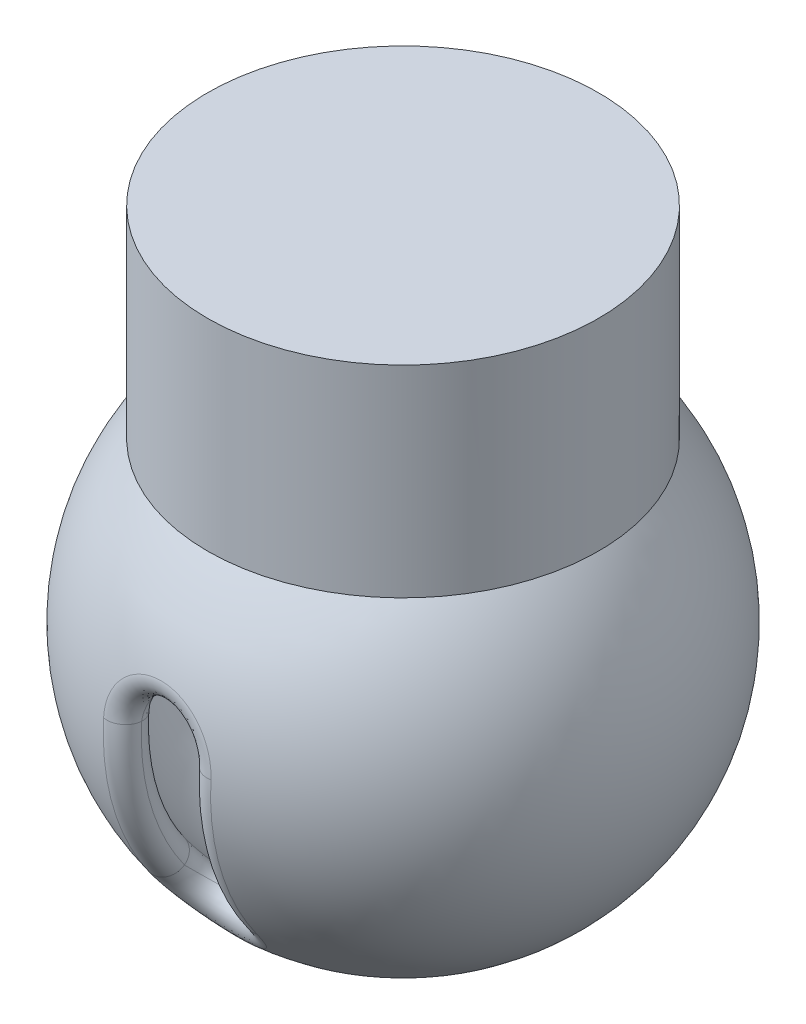
SolidWorks part; units mm, degrees
ref_plane "Front Plane" through (0, 0, 0) normal (0, 0, 1) x (1, 0, 0)
ref_plane "Top Plane" through (0, 0, 0) normal (0, 1, 0) x (1, 0, 0)
ref_plane "Right Plane" through (0, 0, 0) normal (1, 0, 0) x (0, 0, -1)
sketch "Sketch1" plane through (0, 0, 0) normal (0, 0, 1) x (1, 0, 0)
  line L0 (0, 11.6) -> (0, -11.6)
  arc A0 (0, 11.6) -> (0, -11.6) centre (0, 0) cw
  dimension "D1" = 23.2
revolve "Revolve1" add sketch "Sketch1" angle 360 about L0
sketch "Sketch2" plane through (0, 0, 0) normal (0, 1, 0) x (1, 0, 0)
  circle A0 centre (0, 0) radius 5
  dimension "D1" = 10
extrude "Cut-Extrude1" cut sketch "Sketch2" against normal up to next
shell "Shell1" thickness 1.6 removed face at (0, 0, 5) removed face at (0, 0, 5)
fillet "Fillet1" radius 0.8 2 edges at (0, -8.6603, 5) (0, -10.4671, 5)
ref_plane "Plane1" through (0, 11.6, 0) normal (0, 1, 0) x (1, 0, 0)
sketch "Sketch3" plane through (0, 11.6, 0) normal (0, 1, 0) x (1, 0, 0)
  circle A0 centre (0, 0) radius 9
  dimension "D1" = 18
extrude "Boss-Extrude1" add sketch "Sketch3" along normal blind 5 and the other way up to next
ref_axis "Axis1" through (0, 7.3185, 0) along (0, 1, 0)
ref_point "bottom center"
sketch "Sketch5" plane through (0, 0, 0) normal (1, 0, 0) x (0, 0, -1)
  line L0 (0, 10) -> (-11.5969, 0.2691) construction
  line L1 (0, 10) -> (-9.5637, -6.5648) construction
  line L3 (0, 7.3185) -> (0, 16.6) construction
  line L4 (0, 10) -> (-11.1309, -3.2653) construction
  arc A0 (-9, 7.3185) -> (-6.2296, -9.7853) centre (0, 0) ccw construction
  point P11 (-11.1309, -3.2653)
  dimension "D1" = 30
  dimension "D2" = 50
  dimension "D3" = 40
ref_plane "Plane2" through (0, -3.2653, 11.1309) normal (0, -0.2815, 0.9596) x (1, 0, 0)
sketch "Sketch6" plane through (0, -3.2653, 11.1309) normal (0, -0.2815, 0.9596) x (1, 0, 0)
  line L0 (0, 11.4711) -> (0, -13.8233) construction
  line L1 (-1.5, 3.5) -> (-1.5, -3.5)
  line L2 (1.5, 3.5) -> (1.5, -3.5)
  arc A0 (1.5, -3.5) -> (-1.5, -3.5) centre (0, -3.5) cw
  arc A1 (1.5, 3.5) -> (-1.5, 3.5) centre (0, 3.5) ccw
  point P9 (1.5, 3.5742)
  dimension "D1" = 1.5
  dimension "D2" = 7
  dimension "D3" = 3.5
extrude "Cut-Extrude2" cut sketch "Sketch6" against normal up to next
fillet "Fillet2" radius 0.8 8 edges at (0.3276, -4.7083, 8.8162) (-1.5, -2.7831, 9.4871) (0.3173, 2.3236, 9.7211) (0.103, -7.7412, 8.6385) (-1.5, -3.2379, 11.0375) (-0.0803, 1.8491, 11.4514) (1.5, -2.7831, 9.4871) (1.5, -3.2379, 11.0375)
